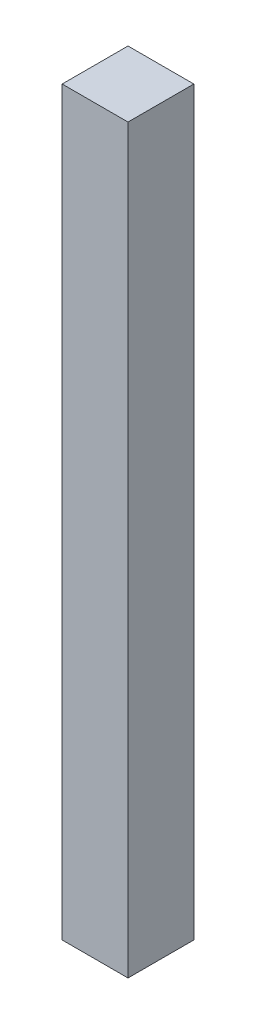
SolidWorks part; units mm, degrees
ref_plane "Front Plane" through (0, 0, 0) normal (0, 0, 1) x (1, 0, 0)
ref_plane "Top Plane" through (0, 0, 0) normal (0, 1, 0) x (1, 0, 0)
ref_plane "Right Plane" through (0, 0, 0) normal (1, 0, 0) x (0, 0, -1)
sketch "Sketch1" plane through (0, 0, 0) normal (0, 1, 0) x (1, 0, 0)
  line L1 (0, 0) -> (25.4, 0)
  line L2 (0, 0) -> (0, 25.4)
  line L3 (0, 25.4) -> (25.4, 25.4)
  line L4 (25.4, 0) -> (25.4, 25.4)
  dimension "D1" = 25.4
  dimension "D2" = 25.4
extrude "Boss-Extrude1" add sketch "Sketch1" along normal blind 609.6
sketch "Sketch3" plane through (0, 0, -25.4) normal (0, 0, -1) x (-1, 0, 0)
  line L0 (0, 609.6) -> (0, 0) construction
  line L1 (0, 466.3042) -> (-25.4, 466.3042)
  line L2 (0, 466.3042) -> (0, 609.6)
  line L3 (0, 609.6) -> (-25.4, 609.6)
  line L4 (-25.4, 466.3042) -> (-25.4, 609.6)
  line L6 (-25.4, 466.3042) -> (0, 466.3042) construction
extrude "Cut-Extrude1" [suppressed] cut sketch "Sketch3" against normal up to surface (25.4 mm away) up to face at (12.7, 304.8, 0)
sketch "Sketch4" [suppressed] plane through (0, 0, 0) normal (0, 0, 1) x (1, 0, 0)
  line L0 (0, 609.6) -> (0, 0) construction
  line L1 (0, 276.4933) -> (25.4, 276.4933)
  line L2 (0, 276.4933) -> (0, 609.6)
  line L3 (0, 609.6) -> (25.4, 609.6)
  line L4 (25.4, 276.4933) -> (25.4, 609.6)
  line L6 (0, 276.4933) -> (25.4, 276.4933) construction
extrude "Cut-Extrude2" [suppressed] cut sketch "Sketch4" against normal up to surface (430.6021 mm away) up to face at (12.7, 304.8, -25.4)
sketch "Sketch5" plane through (0, 0, -25.4) normal (0, 0, -1) x (-1, 0, 0)
  line L0 (0, 609.6) -> (0, 0) construction
  line L1 (0, 571.9407) -> (-25.4, 571.9407)
  line L2 (0, 571.9407) -> (0, 609.6)
  line L3 (0, 609.6) -> (-25.4, 609.6)
  line L4 (-25.4, 571.9407) -> (-25.4, 609.6)
extrude "Cut-Extrude3" cut sketch "Sketch5" against normal up to surface (25.4 mm away) up to face at (12.7, 304.8, 0)
sketch "Sketch6" [suppressed] plane through (0, 0, -25.4) normal (0, 0, -1) x (-1, 0, 0)
  line L0 (0, 609.6) -> (0, 0) construction
  line L1 (0, 553.696) -> (-25.4, 553.696)
  line L2 (0, 553.696) -> (0, 609.6)
  line L3 (0, 609.6) -> (-25.4, 609.6)
  line L4 (-25.4, 553.696) -> (-25.4, 609.6)
  line L6 (-25.4, 553.696) -> (0, 553.696) construction
extrude "Cut-Extrude4" [suppressed] cut sketch "Sketch6" against normal up to surface (25.4 mm away) up to face at (12.7, 285.9703, 0)
sketch "Sketch7" [suppressed] plane through (0, 0, 0) normal (0, 0, 1) x (1, 0, 0)
  line L0 (25.4, 609.6) -> (25.4, 0) construction
  line L1 (25.4, 422.1079) -> (0, 422.1079)
  line L2 (25.4, 422.1079) -> (25.4, 609.6)
  line L3 (25.4, 609.6) -> (0, 609.6)
  line L4 (0, 422.1079) -> (0, 609.6)
  line L8 (0, 422.1079) -> (25.4, 422.1079) construction
extrude "Cut-Extrude5" [suppressed] cut sketch "Sketch7" against normal up to surface (25.4 mm away) up to face at (12.7, 285.9703, -25.4)
sketch "Sketch8" [suppressed] plane through (0, 0, -25.4) normal (0, 0, -1) x (-1, 0, 0)
  line L0 (0, 609.6) -> (0, 0) construction
  line L1 (0, 319.3022) -> (-25.4, 319.3022)
  line L2 (0, 319.3022) -> (0, 609.6)
  line L3 (0, 609.6) -> (-25.4, 609.6)
  line L4 (-25.4, 319.3022) -> (-25.4, 609.6)
  line L6 (-25.4, 319.3022) -> (0, 319.3022) construction
extrude "Cut-Extrude6" [suppressed] cut sketch "Sketch8" against normal up to surface (25.4 mm away) up to face at (12.7, 285.9703, 0)
sketch "Sketch9" [suppressed] plane through (0, 0, 0) normal (0, 0, 1) x (1, 0, 0)
  line L0 (0, 609.6) -> (0, 0) construction
  line L1 (0, 329.8783) -> (25.4, 329.8783)
  line L2 (0, 329.8783) -> (0, 609.6)
  line L3 (0, 609.6) -> (25.4, 609.6)
  line L4 (25.4, 329.8783) -> (25.4, 609.6)
  line L6 (0, 329.8783) -> (25.4, 329.8783) construction
extrude "Cut-Extrude7" [suppressed] cut sketch "Sketch9" against normal up to surface (25.4 mm away) up to face at (12.7, 285.9703, -25.4)
sketch "Sketch10" [suppressed] plane through (25.4, 0, 0) normal (1, 0, 0) x (0, 0, -1)
  line L1 (25.4, 329.8783) -> (0, 329.8783)
  line L2 (25.4, 329.8783) -> (25.4, 0)
  line L3 (25.4, 0) -> (0, 0)
  line L4 (0, 329.8783) -> (0, 0)
extrude "Boss-Extrude2" [suppressed] add sketch "Sketch10" along normal blind 25.4
sketch "Sketch11" [suppressed] plane through (0, 0, -25.4) normal (0, 0, -1) x (-1, 0, 0)
  line L1 (0, 329.8783) -> (-50.8, 329.8783)
  line L2 (0, 329.8783) -> (0, 0)
  line L3 (0, 0) -> (-50.8, 0)
  line L4 (-50.8, 329.8783) -> (-50.8, 0)
extrude "Boss-Extrude3" [suppressed] add sketch "Sketch11" along normal blind 25.4
sketch "Sketch12" [suppressed] plane through (0, 0, 0) normal (0, 0, 1) x (1, 0, 0)
  line L1 (25.4, 319.3022) -> (0, 319.3022)
  line L2 (25.4, 319.3022) -> (25.4, 0)
  line L3 (25.4, 0) -> (0, 0)
  line L4 (0, 319.3022) -> (0, 0)
extrude "Boss-Extrude4" [suppressed] add sketch "Sketch12" along normal blind 25.4
sketch "Sketch13" [suppressed] plane through (25.4, 0, 0) normal (1, 0, 0) x (0, 0, -1)
  line L0 (-25.4, 0) -> (25.4, 0) construction
  line L1 (25.4, 319.3022) -> (-25.4, 319.3022)
  line L2 (25.4, 319.3022) -> (25.4, 0)
  line L3 (25.4, 0) -> (-25.4, 0)
  line L4 (-25.4, 319.3022) -> (-25.4, 0)
  line L5 (-25.4, 0) -> (-25.4, 319.3022) construction
extrude "Boss-Extrude5" [suppressed] add sketch "Sketch13" along normal blind 25.4
sketch "Sketch14" [suppressed] plane through (0, 0, -25.4) normal (0, 0, -1) x (-1, 0, 0)
  line L0 (-25.4, 422.1079) -> (-25.4, 0) construction
  line L1 (-25.4, 422.1079) -> (0, 422.1079)
  line L2 (-25.4, 422.1079) -> (-25.4, 0)
  line L3 (-25.4, 0) -> (0, 0)
  line L4 (0, 422.1079) -> (0, 0)
extrude "Boss-Extrude6" [suppressed] add sketch "Sketch14" along normal blind 25.4
sketch "Sketch15" [suppressed] plane through (25.4, 0, 0) normal (1, 0, 0) x (0, 0, -1)
  line L1 (50.8, 422.1079) -> (0, 422.1079)
  line L2 (50.8, 422.1079) -> (50.8, 0)
  line L3 (50.8, 0) -> (0, 0)
  line L4 (0, 422.1079) -> (0, 0)
extrude "Boss-Extrude7" [suppressed] add sketch "Sketch15" along normal blind 25.4
sketch "Sketch16" plane through (0, 0, 0) normal (0, 0, 1) x (1, 0, 0)
  line L1 (25.4, 571.9407) -> (0, 571.9407)
  line L2 (25.4, 571.9407) -> (25.4, 0)
  line L3 (25.4, 0) -> (0, 0)
  line L4 (0, 571.9407) -> (0, 0)
extrude "Boss-Extrude8" add sketch "Sketch16" along normal blind 25.4
sketch "Sketch17" plane through (25.4, 0, 0) normal (1, 0, 0) x (0, 0, -1)
  line L1 (25.4, 571.9407) -> (-25.4, 571.9407)
  line L2 (25.4, 571.9407) -> (25.4, 0)
  line L3 (25.4, 0) -> (-25.4, 0)
  line L4 (-25.4, 571.9407) -> (-25.4, 0)
extrude "Boss-Extrude9" add sketch "Sketch17" along normal blind 25.4
sketch "Sketch18" [suppressed] plane through (0, 0, -25.4) normal (0, 0, -1) x (-1, 0, 0)
  line L1 (0, 276.4933) -> (-25.4, 276.4933)
  line L2 (0, 276.4933) -> (0, 0)
  line L3 (0, 0) -> (-25.4, 0)
  line L4 (-25.4, 276.4933) -> (-25.4, 0)
extrude "Boss-Extrude10" [suppressed] add sketch "Sketch18" along normal blind 25.4
sketch "Sketch19" [suppressed] plane through (25.4, 0, 0) normal (1, 0, 0) x (0, 0, -1)
  line L1 (50.8, 276.4933) -> (0, 276.4933)
  line L2 (50.8, 276.4933) -> (50.8, 0)
  line L3 (50.8, 0) -> (0, 0)
  line L4 (0, 276.4933) -> (0, 0)
extrude "Boss-Extrude11" [suppressed] add sketch "Sketch19" along normal blind 25.4
sketch "Sketch20" [suppressed] plane through (0, 0, 0) normal (0, 0, 1) x (1, 0, 0)
  line L1 (25.4, 466.3042) -> (0, 466.3042)
  line L2 (25.4, 466.3042) -> (25.4, 0)
  line L3 (25.4, 0) -> (0, 0)
  line L4 (0, 466.3042) -> (0, 0)
extrude "Boss-Extrude12" [suppressed] add sketch "Sketch20" along normal blind 25.4
sketch "Sketch21" [suppressed] plane through (25.4, 0, 0) normal (1, 0, 0) x (0, 0, -1)
  line L0 (-25.4, 0) -> (25.4, 0) construction
  line L1 (-25.4, 466.3042) -> (25.4, 466.3042)
  line L2 (-25.4, 466.3042) -> (-25.4, 0)
  line L3 (-25.4, 0) -> (25.4, 0)
  line L4 (25.4, 466.3042) -> (25.4, 0)
  dimension "D1" = 50.8
extrude "Boss-Extrude13" [suppressed] add sketch "Sketch21" along normal blind 25.4
